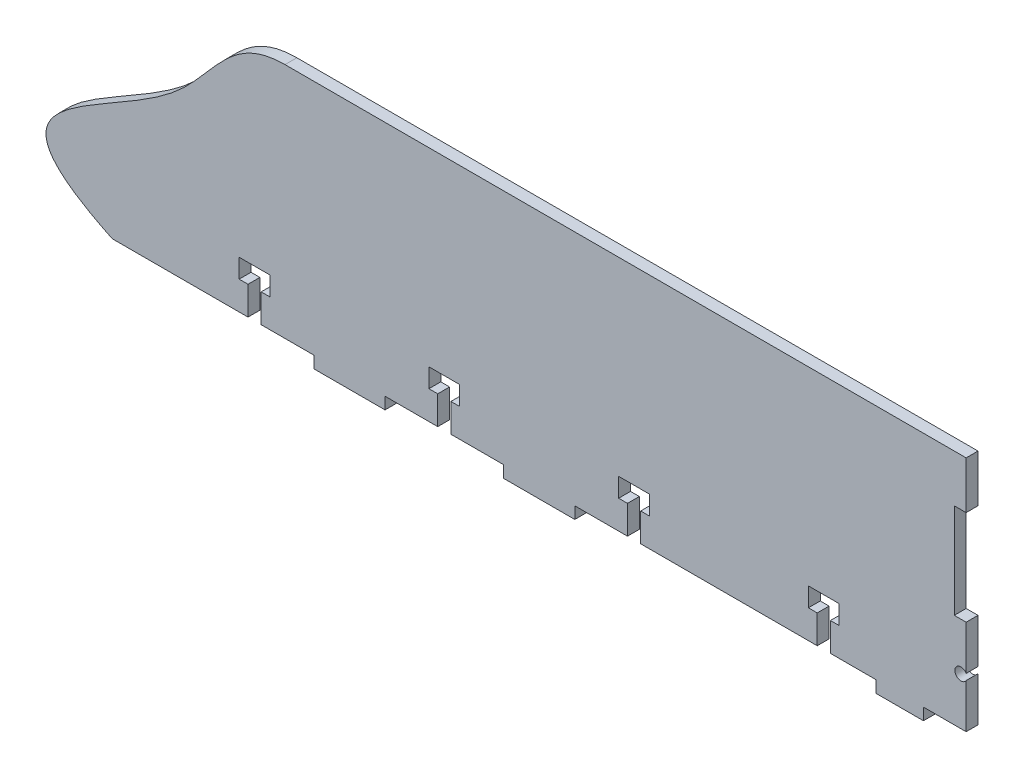
SolidWorks part; units mm, degrees
ref_plane "Front Plane" through (0, 0, 0) normal (0, 0, 1) x (1, 0, 0)
ref_plane "Top Plane" through (0, 0, 0) normal (0, 1, 0) x (1, 0, 0)
ref_plane "Right Plane" through (0, 0, 0) normal (1, 0, 0) x (0, 0, -1)
sketch "Sketch1" plane through (0, 0, 0) normal (0, 0, 1) x (1, 0, 0)
  line L0 (-76.2, -31.75) -> (-76.2, -10.2034) construction
  line L1 (-68.0501, 31.75) -> (111.125, 31.75)
  line L2 (111.125, 31.75) -> (114.3, 31.75)
  line L3 (-114.3, -31.75) -> (-77.9653, -31.75)
  line L4 (114.3, -18.2294) -> (114.3, -6.35)
  line L5 (-74.4347, -24.13) -> (-72.0725, -24.13)
  line L6 (-29.5275, -19.05) -> (-21.2725, -19.05)
  line L7 (-77.9653, -31.75) -> (-77.9653, -24.13)
  line L8 (-74.4347, -31.75) -> (-60.325, -31.75)
  line L9 (-74.4347, -31.75) -> (-74.4347, -24.13)
  line L10 (-80.3275, -24.13) -> (-77.9653, -24.13)
  line L11 (-80.3275, -24.13) -> (-80.3275, -19.05)
  line L12 (-80.3275, -19.05) -> (-72.0725, -19.05)
  line L13 (-72.0725, -24.13) -> (-72.0725, -19.05)
  line L14 (-21.2725, -24.13) -> (-21.2725, -19.05)
  line L15 (-23.6347, -24.13) -> (-21.2725, -24.13)
  line L16 (-29.5275, -24.13) -> (-27.1653, -24.13)
  line L17 (-27.1653, -31.75) -> (-27.1653, -24.13)
  line L18 (-23.6347, -31.75) -> (-23.6347, -24.13)
  line L19 (-29.5275, -24.13) -> (-29.5275, -19.05)
  line L20 (21.2725, -19.05) -> (29.5275, -19.05)
  line L21 (29.5275, -24.13) -> (29.5275, -19.05)
  line L22 (27.1653, -24.13) -> (29.5275, -24.13)
  line L23 (21.2725, -24.13) -> (23.6347, -24.13)
  line L24 (23.6347, -31.75) -> (23.6347, -24.13)
  line L25 (27.1653, -31.75) -> (27.1653, -24.13)
  line L26 (21.2725, -24.13) -> (21.2725, -19.05)
  line L27 (72.0725, -19.05) -> (80.3275, -19.05)
  line L28 (80.3275, -24.13) -> (80.3275, -19.05)
  line L29 (77.9653, -24.13) -> (80.3275, -24.13)
  line L30 (72.0725, -24.13) -> (74.4347, -24.13)
  line L31 (74.4347, -31.75) -> (74.4347, -24.13)
  line L32 (77.9653, -31.75) -> (77.9653, -24.13)
  line L33 (72.0725, -24.13) -> (72.0725, -19.05)
  line L34 (-23.6347, -31.75) -> (-9.525, -31.75)
  line L35 (27.1653, -31.75) -> (74.4347, -31.75)
  line L36 (77.9653, -31.75) -> (88.1951, -31.75)
  line L37 (114.3, 31.75) -> (114.3, 19.05)
  line L38 (111.125, -31.75) -> (114.3, -31.75)
  line L39 (114.3, -31.75) -> (114.3, -19.8706)
  line L40 (102.87, -31.75) -> (111.125, -31.75)
  line L41 (114.3, 19.05) -> (111.125, 19.05)
  line L42 (9.525, -31.75) -> (23.6347, -31.75)
  line L43 (114.3, -6.35) -> (111.125, -6.35)
  line L44 (111.125, 19.05) -> (111.125, -6.35)
  line L45 (-60.325, -31.75) -> (-60.325, -34.925)
  line L46 (-60.325, -34.925) -> (-41.275, -34.925)
  line L47 (-41.275, -31.75) -> (-41.275, -34.925)
  line L48 (-50.8, -31.75) -> (-41.275, -34.925) construction
  line L49 (-60.325, -34.925) -> (-50.8, -31.75) construction
  line L50 (-41.275, -31.75) -> (-27.1653, -31.75)
  line L51 (-9.525, -31.75) -> (-9.525, -34.925)
  line L52 (-9.525, -34.925) -> (9.525, -34.925)
  line L53 (9.525, -31.75) -> (9.525, -34.925)
  line L54 (0, -31.75) -> (9.525, -34.925) construction
  line L55 (-9.525, -34.925) -> (0, -31.75) construction
  line L56 (88.1951, -31.75) -> (90.17, -31.75)
  line L59 (90.17, -31.75) -> (90.17, -34.925)
  line L60 (90.17, -34.925) -> (102.87, -34.925)
  line L61 (102.87, -31.75) -> (102.87, -34.925)
  arc A0 (114.3, -18.2294) -> (114.3, -19.8706) centre (112.8967, -19.05) ccw
  spline S0 degree 3 poles (-114.3, -31.75) (-155.0429, -12.2404) (-94.5489, -1.3775) (-82.5351, 31.7543) (-68.0501, 31.75) knots 0 0 0 0 0.655069 1 1 1 1
  point P49 (-50.8, -31.75)
  point P56 (0, -31.75)
  dimension "D14" = 228.6
  dimension "D15" = 3.175
  dimension "D13" = 3.2512
  dimension "D2" = 31.75
  dimension "D3" = 63.5
  dimension "D4" = 3.175
  dimension "D5" = 25.4
  dimension "D6" = 7.62
  dimension "D7" = 5.08
  dimension "D8" = 3.5306
  dimension "D9" = 1.7653
  dimension "D10" = 8.255
  dimension "D11" = 4.1275
  dimension "D16" = 3.175
  dimension "D17" = 3.175
  dimension "D18" = 19.05
  dimension "D19" = 19.05
  dimension "D20" = 12.7
  dimension "D21" = 11.43
  dimension "D12" = 4
extrude "Boss-Extrude1" add sketch "Sketch1" along normal blind 3.175
